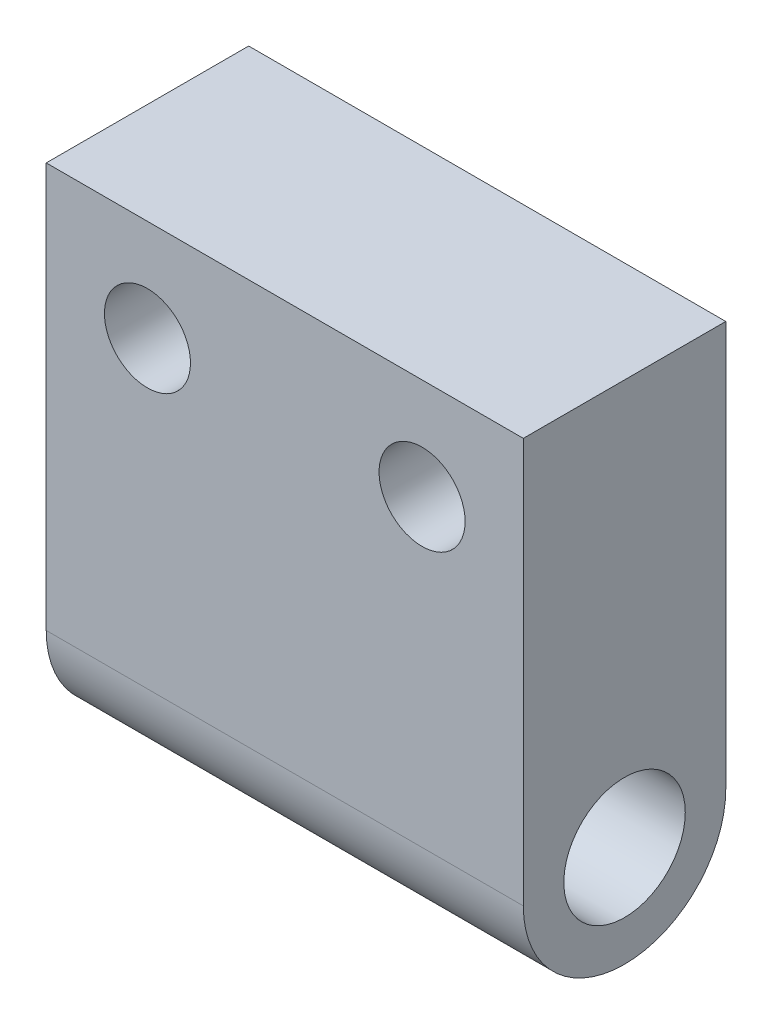
SolidWorks part; units mm, degrees
ref_plane "Front Plane" through (0, 0, 0) normal (0, 0, 1) x (1, 0, 0)
ref_plane "Top Plane" through (0, 0, 0) normal (0, 1, 0) x (1, 0, 0)
ref_plane "Right Plane" through (0, 0, 0) normal (1, 0, 0) x (0, 0, -1)
sketch "Sketch1" plane through (0, 0, 0) normal (0, 0, 1) x (1, 0, 0)
  line L1 (0, 0) -> (47.1297, 0)
  line L2 (0, 0) -> (0, 50)
  line L3 (0, 50) -> (47.1297, 50)
  line L4 (47.1297, 0) -> (47.1297, 50)
  dimension "D1" = 50
extrude "Extrude1" add sketch "Sketch1" along normal blind 20
hole_wizard "Ø8.5 (8.5) Diameter Hole1" positions "3DSketch1" profile "Sketch2" hole size "Ø8.5" standard "Ansi Metric"
sketch3d "3DSketch1"
  line L0 (47.1297, 0, 0) -> (47.1297, 50, 0) construction
  line L1 (47.1297, 0, 20) -> (47.1297, 0, 0) construction
  point P0 (47.1297, 10, 10)
  dimension "D1" = 10
  dimension "D2" = 10
sketch "Sketch2" plane through (47.1297, 10, 10) normal (0, 1, 0) x (0, 0, -1)
  line L0 (0, 0) -> (0, 49.6837)
  line L1 (0, 49.6837) -> (4.25, 47.13)
  line L2 (4.25, 47.13) -> (4.25, 0)
  line L5 (4.25, 0) -> (0, 0)
  line L10 (0, 49.6837) -> (-4.25, 47.13) construction
  line L11 (0, -6.35) -> (0, 107.95) construction
  dimension "Hole Dia." = 8.5
  dimension "Hole Depth" = 47.13
  dimension "Drill Angle" = 118
sketch "Sketch3" plane through (47.1297, 0, 0) normal (1, 0, 0) x (0, 0, -1)
  circle A0 centre (-10, 10) radius 6
sketch "Sketch4" plane through (0, 0, 0) normal (-1, 0, 0) x (0, 0, 1)
  circle A0 centre (10, 10) radius 6
extrude "Extrude2" cut sketch "Sketch4" against normal blind 10
extrude "Extrude3" cut sketch "Sketch3" against normal blind 10
hole_wizard "Ø8.5 (8.5) Diameter Hole2" positions "3DSketch3" profile "Sketch7" hole size "Ø8.5" standard "Ansi Metric" end condition through all
sketch3d "3DSketch3"
  line L0 (47.1297, 0, 20) -> (47.1297, 50, 20) construction
  line L1 (0, 50, 20) -> (0, 0, 20) construction
  line L2 (47.1297, 50, 20) -> (0, 50, 20) construction
  point P0 (37.1297, 40, 20)
  point P2 (10, 40, 20)
  dimension "D1" = 10
  dimension "D2" = 10
  dimension "D3" = 10
  dimension "D4" = 10
sketch "Sketch7" plane through (37.1297, 40, 20) normal (1, 0, 0) x (0, -1, 0)
  line L0 (0, 0) -> (0, 20)
  line L1 (0, 20) -> (4.25, 20)
  line L2 (4.25, 20) -> (4.25, 0)
  line L5 (4.25, 0) -> (0, 0)
  line L11 (0, -6.35) -> (0, 107.95) construction
  dimension "Thru Hole Dia." = 8.5
  dimension "Thru Hole Depth" = 20
fillet "Fillet1" radius 10 2 edges at (23.5649, 0, 20) (23.5649, 0, 0)
equation "\"D1@3DSketch1\" = \"D1@Extrude1\" / 2"
